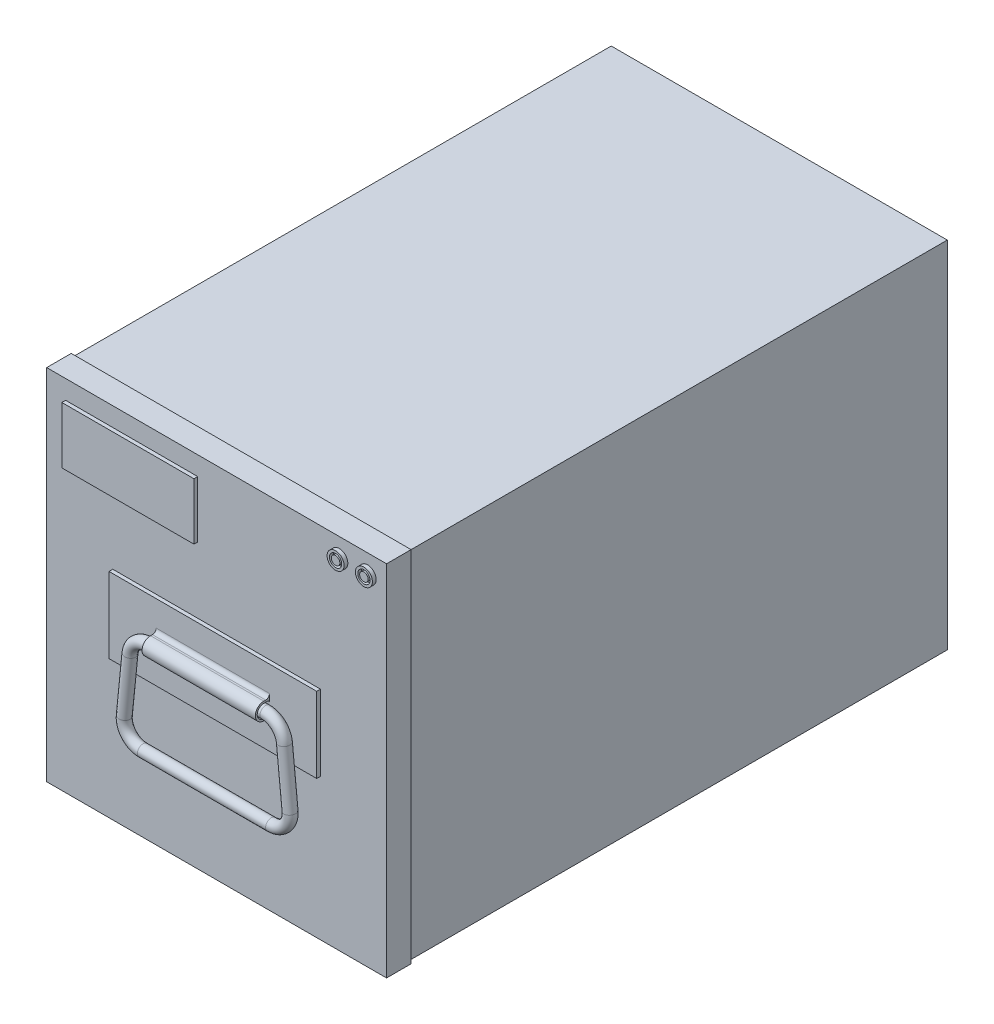
SolidWorks part; units mm, degrees
note: The reader was unsure of these and kept them because the rebuilt part matched: shared geometry of "草图1<4>", "草图13<3>", "草图4<8>".
ref_plane "前视基准面" through (0, 0, 0) normal (0, 0, 1) x (1, 0, 0)
ref_plane "上视基准面" through (0, 0, 0) normal (0, 1, 0) x (1, 0, 0)
ref_plane "右视基准面" through (0, 0, 0) normal (1, 0, 0) x (0, 0, -1)
sketch "草图1" plane through (0, 0, 0) normal (0, 0, 1) x (1, 0, 0)
  line L1 (90, 95) -> (-90, 95)
  line L2 (90, 95) -> (90, -95)
  line L3 (90, -95) -> (-90, -95)
  line L4 (-90, 95) -> (-90, -95)
  line L5 (90, 95) -> (-90, -95) construction
  line L6 (90, -95) -> (-90, 95) construction
  line L7 (89, 94) -> (-89, 94)
  line L8 (89, 94) -> (89, -94)
  line L9 (89, -94) -> (-89, -94)
  line L10 (-89, 94) -> (-89, -94)
  line L11 (89, 94) -> (-89, -94) construction
  line L12 (89, -94) -> (-89, 94) construction
  point P0 (0, 0)
  point P6 (0, 0)
  dimension "D1" = 180
  dimension "D2" = 190
  dimension "D3" = 1
  dimension "D4" = 1
extrude "凸台-拉伸2" add sketch "草图1" along normal blind 13 contours L1 L4 L3 L2
extrude "凸台-拉伸3" add sketch "草图1<4>" against normal blind 285 contours L10 L9 L8 L7
sketch "草图1<4>" plane through (0, 0, 0) normal (0, 0, 1) x (1, 0, 0) same geometry as "草图1"
sketch "草图2" plane through (0, 0, 13) normal (0, 0, 1) x (1, 0, 0)
  line L0 (-90, 95) -> (-90, -95) construction
  line L1 (-80, 85) -> (-10, 85)
  line L2 (-80, 85) -> (-80, 55)
  line L3 (-80, 55) -> (-10, 55)
  line L4 (-10, 85) -> (-10, 55)
  line L5 (-80, 85) -> (-10, 55) construction
  line L6 (-80, 55) -> (-10, 85) construction
  line L7 (90, 95) -> (-90, 95) construction
  line L9 (-55, 20) -> (55, 20)
  line L10 (-55, 20) -> (-55, -20)
  line L11 (-55, -20) -> (55, -20)
  line L12 (55, 20) -> (55, -20)
  line L13 (-55, 20) -> (55, -20) construction
  line L14 (-55, -20) -> (55, 20) construction
  point P0 (-45, 70)
  point P7 (-80, 70)
  point P10 (0, 0)
  dimension "D1" = 10
  dimension "D2" = 70
  dimension "D3" = 30
  dimension "D4" = 10
  dimension "D5" = 110
  dimension "D6" = 40
extrude "凸台-拉伸4" add sketch "草图2" along normal blind 2
sketch "草图3" plane through (0, 0, 15) normal (0, 0, 1) x (1, 0, 0)
  line L0 (-30.9501, 0) -> (30.9501, 0)
  line L1 (-33.9501, -50) -> (33.9501, -50)
  line L2 (0, 11.4458) -> (0, -58.7951) construction
  line L3 (-40.9005, -9.005) -> (-43.9005, -39.005)
  line L4 (43.9005, -39.005) -> (40.9005, -9.005)
  arc A0 (30.9501, 0) -> (40.9005, -9.005) centre (30.9501, -10) cw
  arc A1 (43.9005, -39.005) -> (33.9501, -50) centre (33.9501, -40) cw
  arc A2 (-33.9501, -50) -> (-43.9005, -39.005) centre (-33.9501, -40) cw
  arc A3 (-40.9005, -9.005) -> (-30.9501, 0) centre (-30.9501, -10) cw
  point P3 (0, 0)
  point P8 (0, -50)
  point P12 (40, 0)
  point P15 (45, -50)
  point P19 (-40, 0)
  dimension "D4" = 10
  dimension "D1" = 80
  dimension "D3" = 50
ref_plane "基准面1" through (0, 0, 0) normal (1, 0, 0) x (0, 0, -1)
sketch "草图4" plane through (0, 0, 0) normal (1, 0, 0) x (0, 0, -1)
  line L0 (-15, -20) -> (-13, -20) construction
  line L1 (-13, 95) -> (-13, -95) construction
  line L2 (-15, 20) -> (-13, 20) construction
  line L4 (-15, -20) -> (-13, -20)
  line L5 (-13, 95) -> (-13, -95)
  line L6 (-15, 20) -> (-13, 20)
  line L8 (5.6691, 0) -> (-40.8595, 0) construction
  line L9 (-18, 3.5) -> (-15, 3.5)
  line L10 (-18, -3.5) -> (-15, -3.5)
  line L11 (-15, 20) -> (-15, -20)
  line L12 (-15, 0) -> (-15, -9.005) construction
  circle A0 centre (-18, 0) radius 3
  arc A1 (-18, 3.5) -> (-18, -3.5) centre (-18, 0) ccw
  point P21 (-15, 3.5)
  dimension "D1" = 6
  dimension "D2" = 3.5
sweep "扫描2" add profiles "草图4" path "草图3"
sketch "草图13" plane through (0, 0, 13) normal (0, 0, 1) x (1, 0, 0)
  line L0 (90, 95) -> (90, -95) construction
  line L1 (90, 95) -> (-90, 95) construction
  line L2 (90, 85) -> (56.024, 85) construction
  circle A0 centre (65, 85) radius 4.5
  circle A1 centre (80, 85) radius 4.5
  circle A2 centre (80, 85) radius 2.25
  circle A3 centre (65, 85) radius 2.25
  dimension "D1" = 9
  dimension "D5" = 4.5
  dimension "D2" = 10
  dimension "D3" = 10
  dimension "D4" = 15
extrude "凸台-拉伸5" add sketch "草图13" along normal blind 2 contours A0 | A1
extrude "切除-拉伸-薄壁1" cut sketch "草图13<3>" along normal up to surface (2 mm away) thin contours A3 | A2
sketch "草图13<3>" plane through (0, 0, 13) normal (0, 0, 1) x (1, 0, 0) same geometry as "草图13"
extrude "拉伸-薄壁1" add sketch "草图4<8>" along normal mid plane 60 thin contours L10 A1 L9 thin type one direction reverse wall 1
sketch "草图4<8>" plane through (0, 0, 0) normal (1, 0, 0) x (0, 0, -1) same geometry as "草图4"
fillet "圆角1" radius 2 2 edges at (0, -4.5, 15) (0, 4.5, 15)
fillet "圆角2" radius 1 2 edges at (0, -3.5, 15) (0, 3.5, 15)
